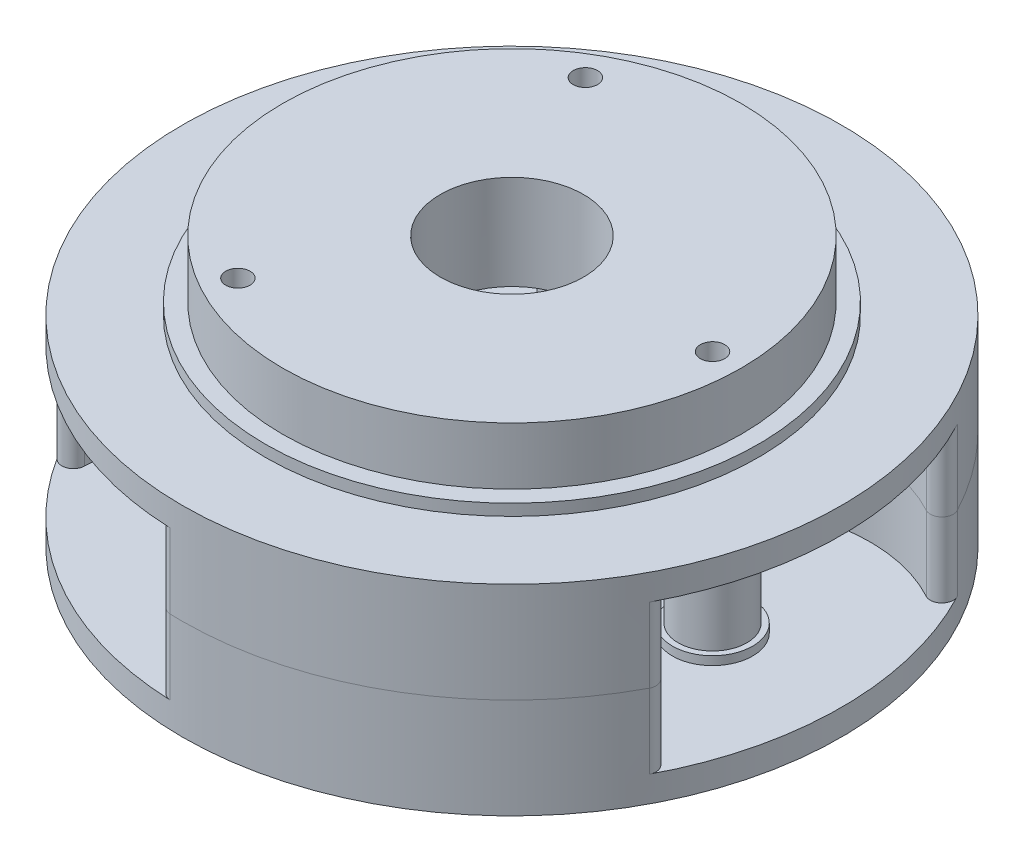
SolidWorks part; units mm, degrees
note: '?' marks a value the reader was unsure of.
ref_plane "Front Plane" through (0, 0, 0) normal (0, 0, 1) x (1, 0, 0)
ref_plane "Top Plane" through (0, 0, 0) normal (0, 1, 0) x (1, 0, 0)
ref_plane "Right Plane" through (0, 0, 0) normal (1, 0, 0) x (0, 0, -1)
ref_axis "Axis1" through (0, 32.45, 0) along (0, -1, 0)?
sketch "Sketch1" plane through (0, 0, 0) normal (1, 0, 0) x (0, 0, -1)
  line L0 (0, 40.8269) -> (0, -40.8269) construction
  line L1 (12.5, 29.5) -> (12.5, -29.5)
  line L2 (12.5, -29.5) -> (40, -29.5)
  line L3 (40, -29.5) -> (40, -19.5)
  line L4 (40, -19.5) -> (43, -19.5)
  line L5 (43, -19.5) -> (43, -17.5)
  line L6 (43, -17.5) -> (57.5, -17.5)
  line L7 (57.5, -17.5) -> (57.5, 17.5)
  line L8 (57.5, 17.5) -> (43, 17.5)
  line L9 (43, 17.5) -> (43, 19.5)
  line L10 (43, 19.5) -> (40, 19.5)
  line L11 (40, 19.5) -> (40, 29.5)
  line L12 (40, 29.5) -> (12.5, 29.5)
  line L13 (0, 0) -> (12.5, 0) construction
  line L14 (10, 29.5) -> (10, -29.5) construction
  line L15 (60, 29.5) -> (60, -43.7209) construction
  line L16 (57.5, 17.5) -> (60, 17.5) construction
  line L17 (12.5, 29.5) -> (10, 29.5) construction
  line L18 (43, 17.5) -> (43, 12.5) construction
  line L19 (43, 12.5) -> (43, -12.5) construction
  line L20 (43, -12.5) -> (43, -17.5) construction
  point P21 (10, 0)
  point P25 (43.4107, 17.5)
  dimension "D1" = 80
  dimension "D2" = 25
  dimension "D3" = 10
  dimension "D4" = 2
  dimension "D5" = 10
  dimension "D6" = 60
  dimension "D7" = 3
  dimension "D8" = 2.5
  dimension "D9" = 5
revolve "Revolve1" add sketch "Sketch1" angle 360 about L0
sketch "Sketch2" plane through (0, 0, 0) normal (0, 1, 0) x (1, 0, 0)
  circle A0 centre (0, 0) radius 35 construction
  circle A1 centre (35, 0) radius 27.5
  circle A4 centre (35, 0) radius 7
  point P11 (0, 0)
  dimension "D1" = 55
  dimension "D2" = 70
  dimension "D3" = 14
extrude "Planet Cutout" cut sketch "Sketch2" against normal mid plane 26
fillet "Planet Cutout Fillet" radius 2 4 edges at (53.9286, 0, 19.9489) (53.9286, 0, -19.9489) (8.9286, 0, -8.7482) (8.9286, 0, 8.7482)
sketch "Sketch3" plane through (0, 0, 0) normal (0, 1, 0) x (1, 0, 0)
  circle A0 centre (35, 0) radius 6
  arc A1 (48.1174, 24.1699) -> (9.8971, 11.2292) centre (35, 0) ccw construction
  dimension "D1" = 12
extrude "Planet Bearing Cutout" cut sketch "Sketch3" against normal mid plane 23 thin
sketch "Sketch5" plane through (0, 0, 0) normal (0, 1, 0) x (1, 0, 0)
  circle A0 centre (35, 0) radius 2.125
  circle A1 centre (35, 0) radius 6 construction
  dimension "D1" = 4.25
extrude "Planet Pin Hole" cut sketch "Sketch5" along normal through all and the other way offset from surface (24.5 mm away) 5 other way up to face at (0, -29.5, 40)
pattern_circular "Planet Cutout Pattern" count 3 over 360 about axis through (0, 0, 0) along (0, 1, 0) of "Planet Cutout", "Planet Cutout Fillet", "Planet Bearing Cutout", "Planet Pin Hole"
split "Split1" trim tools "Top Plane" bodies to split 103 resulting bodies 106 107
sketch "Sketch6" plane through (0, 0, 0) normal (0, 1, 0) x (1, 0, 0)
  arc A1 (41.6498, 35.1503) -> (9.6162, 53.6449) centre (0, 0) ccw
  arc A3 (12.8932, 27.7605) -> (6.7059, 48.8668) centre (-17.5, 30.3109) ccw
  arc A7 (38.967, 30.2409) -> (17.5947, 25.046) centre (35, 0) ccw
  arc A8 (48.1174, 24.1699) -> (50.8398, 26.862) centre (49.0714, 25.9277) ccw
  arc A9 (50.8398, 26.862) -> (-2.1567, 57.4595) centre (0, 0) ccw
  arc A10 (-2.1567, 57.4595) -> (-3.127, 53.7559) centre (-2.0817, 55.4609) ccw
  arc A11 (4.7762, 14.1857) -> (-3.127, 53.7559) centre (-17.5, 30.3109) ccw
  arc A12 (4.7762, 14.1857) -> (5.514, 11.2181) centre (6.3963, 13.013) ccw
  arc A13 (6.9581, 10.3843) -> (5.514, 11.2181) centre (0, 0) ccw
  arc A14 (6.9581, 10.3843) -> (9.8971, 11.2292) centre (8.0714, 12.0458) ccw
  arc A15 (48.1174, 24.1699) -> (9.8971, 11.2292) centre (35, 0) ccw
  arc A16 (48.1174, 24.1699) -> (50.8398, 26.862) centre (49.0714, 25.9277) ccw construction
  arc A17 (50.8398, 26.862) -> (-2.1567, 57.4595) centre (0, 0) ccw construction
  arc A18 (-2.1567, 57.4595) -> (-3.127, 53.7559) centre (-2.0817, 55.4609) ccw construction
  arc A19 (4.7762, 14.1857) -> (-3.127, 53.7559) centre (-17.5, 30.3109) ccw construction
  arc A20 (4.7762, 14.1857) -> (5.514, 11.2181) centre (6.3963, 13.013) ccw construction
  arc A21 (6.9581, 10.3843) -> (5.514, 11.2181) centre (0, 0) ccw construction
  arc A22 (6.9581, 10.3843) -> (9.8971, 11.2292) centre (8.0714, 12.0458) ccw construction
  arc A23 (48.1174, 24.1699) -> (9.8971, 11.2292) centre (35, 0) ccw construction
  arc A24 (46.6429, 28.1903) -> (1.0921, 54.4891) centre (0, 0) ccw construction
  arc A25 (46.6429, 28.1903) -> (10.4456, 18.0923) centre (35, 0) ccw construction
  arc A26 (41.6498, 35.1503) -> (38.967, 30.2409) centre (39.3571, 33.2154) cw
  arc A27 (10.4456, 18.0923) -> (1.0921, 54.4891) centre (-17.5, 30.3109) ccw construction
  arc A28 (17.5947, 25.046) -> (12.8932, 27.7605) centre (15.8827, 27.5096) cw
  arc A29 (9.6162, 53.6449) -> (6.7059, 48.8668) centre (9.0868, 50.692) ccw
  arc A32 (46.6429, 28.1903) -> (46.6429, 28.1903) centre (46.6429, 28.1903) ccw construction
  arc A33 (10.4456, 18.0923) -> (10.4456, 18.0923) centre (10.4456, 18.0923) cw construction
  arc A34 (10.4456, 18.0923) -> (10.4456, 18.0923) centre (10.4456, 18.0923) ccw construction
  arc A35 (10.4456, 18.0923) -> (10.4456, 18.0923) centre (10.4456, 18.0923) cw construction
  arc A36 (1.0921, 54.4891) -> (1.0921, 54.4891) centre (1.0921, 54.4891) ccw construction
  dimension "D3" = 3
  dimension "D1" = 0
  dimension "D2" = 3
extrude "Indexing Cutout" cut sketch "Sketch6" against normal blind 1.5
pattern_circular "Indexing Cutout Pattern" count 3 over 360 about axis through (0, 0, 0) along (0, 1, 0) of "Indexing Cutout"
sketch "Sketch9" plane through (0, 0, 0) normal (0, -1, 0) x (1, 0, 0)
  arc A0 (41.4587, -34.9891) -> (38.9995, -30.4888) centre (39.3571, -33.2154) ccw
  arc A1 (17.452, -25.2513) -> (38.9995, -30.4888) centre (35, 0) ccw
  arc A2 (17.452, -25.2513) -> (13.1423, -27.7396) centre (15.8827, -27.5096) ccw
  arc A3 (6.9043, -49.0189) -> (13.1423, -27.7396) centre (-17.5, -30.3109) ccw
  arc A4 (6.9043, -49.0189) -> (9.5721, -53.3989) centre (9.0868, -50.692) ccw
  arc A5 (9.5721, -53.3989) -> (41.4587, -34.9891) centre (0, 0) ccw
  arc A6 (41.6498, -35.1503) -> (38.967, -30.2409) centre (39.3571, -33.2154) ccw
  arc A7 (9.6162, -53.6449) -> (41.6498, -35.1503) centre (0, 0) ccw
  arc A8 (6.7059, -48.8668) -> (9.6162, -53.6449) centre (9.0868, -50.692) ccw
  arc A9 (6.7059, -48.8668) -> (12.8932, -27.7605) centre (-17.5, -30.3109) ccw
  arc A10 (17.5947, -25.046) -> (12.8932, -27.7605) centre (15.8827, -27.5096) ccw
  arc A11 (17.5947, -25.046) -> (38.967, -30.2409) centre (35, 0) ccw
  arc A12 (41.6498, -35.1503) -> (38.967, -30.2409) centre (39.3571, -33.2154) ccw construction
  arc A13 (9.6162, -53.6449) -> (41.6498, -35.1503) centre (0, 0) ccw construction
  arc A14 (6.7059, -48.8668) -> (9.6162, -53.6449) centre (9.0868, -50.692) ccw construction
  arc A15 (6.7059, -48.8668) -> (12.8932, -27.7605) centre (-17.5, -30.3109) ccw construction
  arc A16 (17.5947, -25.046) -> (12.8932, -27.7605) centre (15.8827, -27.5096) ccw construction
  arc A17 (17.5947, -25.046) -> (38.967, -30.2409) centre (35, 0) ccw construction
  arc A18 (-51.0308, -18.4098) -> (-45.9038, -18.5301) centre (-48.444, -17.4766) ccw
  arc A19 (-30.5943, -2.4882) -> (-45.9038, -18.5301) centre (-17.5, -30.3109) ccw
  arc A20 (-30.5943, -2.4882) -> (-30.5943, 2.4882) centre (-31.7653, 0) ccw
  arc A21 (-45.9038, 18.5301) -> (-30.5943, 2.4882) centre (-17.5, 30.3109) ccw
  arc A22 (-45.9038, 18.5301) -> (-51.0308, 18.4098) centre (-48.444, 17.4766) ccw
  arc A23 (-51.0308, 18.4098) -> (-51.0308, -18.4098) centre (0, 0) ccw
  arc A24 (9.5721, 53.3989) -> (6.9043, 49.0189) centre (9.0868, 50.692) ccw
  arc A25 (13.1423, 27.7396) -> (6.9043, 49.0189) centre (-17.5, 30.3109) ccw
  arc A26 (13.1423, 27.7396) -> (17.452, 25.2513) centre (15.8827, 27.5096) ccw
  arc A27 (38.9995, 30.4888) -> (17.452, 25.2513) centre (35, 0) ccw
  arc A28 (38.9995, 30.4888) -> (41.4587, 34.9891) centre (39.3571, 33.2154) ccw
  arc A29 (41.4587, 34.9891) -> (9.5721, 53.3989) centre (0, 0) ccw
  point P48 (0, 0)
  dimension "D1" = 0
  dimension "D2" = 0.25
  dimension "D3" = 3
extrude "Indexing Bosses" add sketch "Sketch9" along normal up to surface (1.5 mm away)
